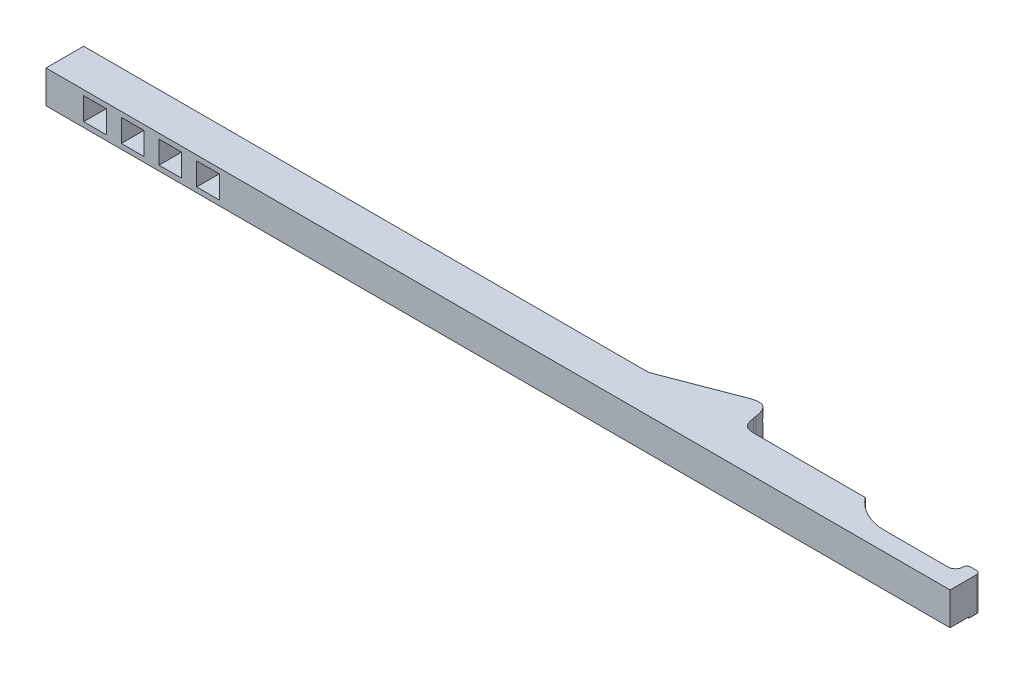
SolidWorks part; units mm, degrees
ref_plane "Plano frontal" through (0, 0, 0) normal (0, 0, 1) x (1, 0, 0)
ref_plane "Plano superior" through (0, 0, 0) normal (0, 1, 0) x (1, 0, 0)
ref_plane "Plano direito" through (0, 0, 0) normal (1, 0, 0) x (0, 0, -1)
sketch "Esboço1" plane through (0, 0, 0) normal (1, 0, 0) x (0, 0, -1)
  line L1 (-5, 2.175) -> (0, 2.175)
  line L2 (-5, 2.175) -> (-5, -2.175)
  line L3 (-5, -2.175) -> (0, -2.175)
  line L4 (0, 2.175) -> (0, -2.175)
  point P4 (0, 0)
  dimension "D1" = 5
  dimension "D2" = 4.35
extrude "Ressalto-extrusão1" add sketch "Esboço1" along normal blind 120
sketch "Esboço2" plane through (0, 2.175, 0) normal (0, 1, 0) x (1, 0, 0)
  line L0 (120, 0) -> (0, 0) construction
  line L1 (75, 0) -> (87.5, 0)
  line L2 (87.5, 0) -> (86.75, 4.5)
  line L3 (86.75, 4.5) -> (75, 0)
  dimension "D2" = 4.5
  dimension "D1" = 45
  dimension "D3" = 0.75
  dimension "D4" = 11.75
extrude "Ressalto-extrusão2" add sketch "Esboço2" against normal blind 4.35
sketch "Esboço3" plane through (0, 2.175, 0) normal (0, 1, 0) x (1, 0, 0)
  line L0 (120, 0) -> (120, -5) construction
  line L1 (-80, -35) -> (120, -35)
  line L2 (-80, -35) -> (-80, -5)
  line L3 (-80, -5) -> (120, -5)
  line L4 (120, -35) -> (120, -5)
  dimension "D1" = 30
  dimension "D2" = 200
  dimension "D3" = 5
extrude "Corte-extrusão1" [suppressed] cut sketch "Esboço3" against normal blind 30
hole_wizard "Ø3.0mm Dowel Hole3" [suppressed] positions "Sketch9" profile "Sketch10" hole size "Ø3.0" standard "ANSI Metric"
sketch "Sketch9" plane through (0, 0, 0) normal (0, 0, -1) x (-1, 0, 0)
  line L1 (-3.5, -1.5) -> (-6.5, -1.5)
  line L2 (-3.5, -1.5) -> (-3.5, 1.5)
  line L3 (-3.5, 1.5) -> (-6.5, 1.5)
  line L4 (-6.5, -1.5) -> (-6.5, 1.5)
  line L5 (-3.5, -1.5) -> (-6.5, 1.5) construction
  line L6 (-3.5, 1.5) -> (-6.5, -1.5) construction
  line L8 (-8.5, -1.5) -> (-11.5, -1.5)
  line L9 (-8.5, -1.5) -> (-8.5, 1.5)
  line L10 (-8.5, 1.5) -> (-11.5, 1.5)
  line L11 (-11.5, -1.5) -> (-11.5, 1.5)
  line L12 (-8.5, -1.5) -> (-11.5, 1.5) construction
  line L13 (-8.5, 1.5) -> (-11.5, -1.5) construction
  line L15 (-13.5, -1.5) -> (-16.5, -1.5)
  line L16 (-13.5, -1.5) -> (-13.5, 1.5)
  line L17 (-13.5, 1.5) -> (-16.5, 1.5)
  line L18 (-16.5, -1.5) -> (-16.5, 1.5)
  line L19 (-13.5, -1.5) -> (-16.5, 1.5) construction
  line L20 (-13.5, 1.5) -> (-16.5, -1.5) construction
  line L22 (-18.5, -1.5) -> (-21.5, -1.5)
  line L23 (-18.5, -1.5) -> (-18.5, 1.5)
  line L24 (-18.5, 1.5) -> (-21.5, 1.5)
  line L25 (-21.5, -1.5) -> (-21.5, 1.5)
  line L26 (-18.5, -1.5) -> (-21.5, 1.5) construction
  line L27 (-18.5, 1.5) -> (-21.5, -1.5) construction
  point P0 (-5, 0)
  point P2 (-10, 0)
  point P4 (-15, 0)
  point P8 (-20, 0)
  point P9 (-5, 0)
  point P78 (-10, 0)
  point P170 (-15, 0)
  point P225 (-20, 0)
  dimension "D1" = 5
  dimension "D2" = 5
  dimension "D3" = 5
  dimension "D4" = 5
  dimension "D5" = 3
sketch "Sketch10" [suppressed] plane through (5, 0, 0) normal (1, 0, 0) x (0, 1, 0)
  line L0 (0, 0) -> (0, 5)
  line L1 (0, 5) -> (1.5, 5)
  line L2 (1.5, 5) -> (1.5, 0)
  line L5 (1.5, 0) -> (0, 0)
  line L11 (0, -6.35) -> (0, 107.95) construction
  dimension "Thru Hole Dia." = 3
  dimension "Thru Hole Depth" = 5
sketch "Sketch12" plane through (0, 2.175, 0) normal (0, 1, 0) x (1, 0, 0)
  line L0 (120, -2.5) -> (108.7805, -2.5)
  line L2 (120, 0) -> (87.5, 0) construction
  line L3 (120, 0) -> (120, -5) construction
  line L4 (103.75, 0) -> (120, 0)
  line L5 (120, 0) -> (120, -2.5)
  arc A0 (108.7805, -2.5) -> (103.75, 0) centre (108.7805, 3.8112) cw
extrude "Cut-Extrude2" cut sketch "Sketch12" against normal blind 10
fillet "Fillet4" [suppressed] radius 3
sketch "Sketch14" plane through (0, 0, 0) normal (0, 0, -1) x (-1, 0, 0)
  line L1 (-4.1209, -0.7527) -> (-5.0144, -0.7527)
  line L2 (-4.1209, -0.7527) -> (-4.1209, 0.8163)
  line L3 (-4.1209, 0.8163) -> (-5.0144, 0.8163)
  line L4 (-5.0144, -0.7527) -> (-5.0144, 0.8163)
extrude "Boss-Extrude1" [suppressed] add sketch "Sketch14" against normal blind 5
fillet "Fillet1" [suppressed] radius 0.5
ref_plane "Plane2" [suppressed] through (82.9, -2.375, 0) normal (0, 0, -1) x (-1, 0, 0)
hole_wizard "Ø3.0mm Dowel Hole1" [suppressed] positions "Sketch3" profile "Sketch4" hole size "Ø3.0" standard "ANSI Metric"
sketch "Sketch3" [suppressed] plane through (0, 0, 5) normal (0, 0, 1) x (1, 0, 0)
  line L0 (0, -2.375) -> (0, 2.375) construction
  point P0 (6, 0)
  point P2 (12, 0)
  point P4 (18, 0)
  point P11 (24, 0)
  dimension "D1" = 6
  dimension "D2" = 6
  dimension "D3" = 6
  dimension "D4" = 6
sketch "Sketch4" plane through (6, 0, 5) normal (1, 0, 0) x (0, -1, 0)
  line L0 (0, 0) -> (0, 13.75)
  line L1 (0, 13.75) -> (1.5, 13.75)
  line L2 (1.5, 13.75) -> (1.5, 0)
  line L5 (1.5, 0) -> (0, 0)
  line L11 (0, -6.35) -> (0, 107.95) construction
  dimension "Thru Hole Dia." = 3
  dimension "Thru Hole Depth" = 13.75
sketch3d "3DSketch2" [suppressed] plane through (0, 0, 0) normal (0, 0, 1) x (1, 0, 0)
fillet "Fillet5" radius 2 1 edges at (86.75, 0, -4.5) conic radius 1
fillet "Fillet6" radius 2 1 edges at (75, 0, 0) conic radius 1
fillet "Fillet7" radius 2 1 edges at (87.5, 0, 0) conic radius 1
sketch "Sketch16" plane through (0, 0, 0) normal (0, 0, 1) x (1, 0, 0)
  line L0 (0, -2.175) -> (0, 2.175) construction
  line L1 (23, -1.5) -> (20, -1.5)
  line L2 (23, -1.5) -> (23, 1.5)
  line L3 (23, 1.5) -> (20, 1.5)
  line L4 (20, -1.5) -> (20, 1.5)
  line L5 (23, -1.5) -> (20, 1.5) construction
  line L6 (23, 1.5) -> (20, -1.5) construction
  line L8 (18, -1.5) -> (15, -1.5)
  line L9 (18, -1.5) -> (18, 1.5)
  line L10 (18, 1.5) -> (15, 1.5)
  line L11 (15, -1.5) -> (15, 1.5)
  line L12 (18, -1.5) -> (15, 1.5) construction
  line L13 (18, 1.5) -> (15, -1.5) construction
  line L15 (13, -1.5) -> (10, -1.5)
  line L16 (13, -1.5) -> (13, 1.5)
  line L17 (13, 1.5) -> (10, 1.5)
  line L18 (10, -1.5) -> (10, 1.5)
  line L19 (13, -1.5) -> (10, 1.5) construction
  line L20 (13, 1.5) -> (10, -1.5) construction
  line L22 (8, -1.5) -> (5, -1.5)
  line L23 (8, -1.5) -> (8, 1.5)
  line L24 (8, 1.5) -> (5, 1.5)
  line L25 (5, -1.5) -> (5, 1.5)
  line L26 (8, -1.5) -> (5, 1.5) construction
  line L27 (8, 1.5) -> (5, -1.5) construction
  point P0 (21.5, 0)
  point P2 (16.5, 0)
  point P4 (11.5, 0)
  point P8 (6.5, 0)
  point P9 (21.5, 0)
  point P78 (16.5, 0)
  point P170 (11.5, 0)
  point P225 (6.5, 0)
  dimension "D1" = 5
  dimension "D2" = 5
  dimension "D3" = 5
  dimension "D4" = 5
  dimension "D5" = 3
extrude "Cut-Extrude3" cut sketch "Sketch16" along normal blind 10
sketch "Sketch17" plane through (0, 0, 2.5) normal (0, 0, -1) x (-1, 0, 0)
  line L0 (-120, 2.175) -> (-120, -2.175) construction
  line L1 (-120, -2.325) -> (-118.2195, -2.325)
  line L2 (-120, -2.325) -> (-120, 2.175)
  line L3 (-120, 2.175) -> (-118.2195, 2.175)
  line L4 (-118.2195, -2.325) -> (-118.2195, 2.175)
  line L5 (-108.7805, 2.175) -> (-120, 2.175) construction
extrude "Boss-Extrude2" add sketch "Sketch17" along normal blind 1.5
fillet "Fillet8" radius 1 1 edges at (118.2195, 0, 2.5)
fillet "Fillet9" radius 0.5 2 edges at (120, -0.075, 1) (118.2195, -0.075, 1)
